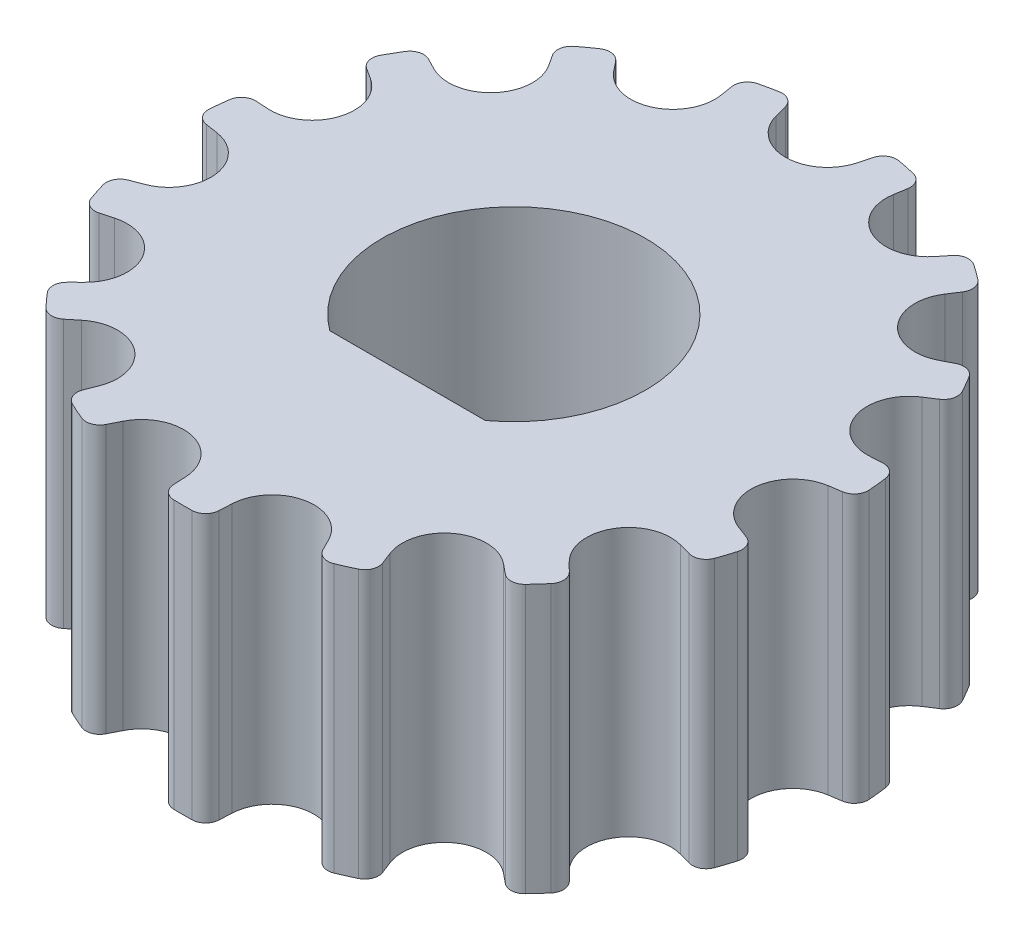
SolidWorks part; units mm, degrees
ref_plane "Front Plane" through (0, 0, 0) normal (0, 0, 1) x (1, 0, 0)
ref_plane "Top Plane" through (0, 0, 0) normal (0, 1, 0) x (1, 0, 0)
ref_plane "Right Plane" through (0, 0, 0) normal (1, 0, 0) x (0, 0, -1)
sketch "Sketch1" plane through (0, 0, 0) normal (0, 1, 0) x (1, 0, 0)
  circle A0 centre (0, 0) radius 7.162
  dimension "D1" = 14.3239
extrude "Boss-Extrude1" add sketch "Sketch1" along normal blind 5.8
sketch "Sketch2" plane through (0, 5.8, 0) normal (0, 1, 0) x (1, 0, 0)
  line L0 (0, 0) -> (0, 7.162) construction
  line L1 (-0.8799, 6.5598) -> (-0.95, 6.8255)
  line L2 (-2.913, 6.5428) -> (-2.913, 7.162)
  line L3 (-2.913, 7.162) -> (2.913, 7.162)
  line L4 (0.8799, 6.5598) -> (0.95, 6.8255)
  line L5 (2.913, 6.5428) -> (2.913, 7.162)
  circle A0 centre (0, 0) radius 7.162 construction
  arc A1 (0.8799, 6.5598) -> (-0.8799, 6.5598) centre (0, 6.792) cw
  arc A2 (-0.95, 6.8255) -> (-1.2943, 7.0441) centre (-1.2401, 6.749) ccw
  arc A4 (0.95, 6.8255) -> (1.2943, 7.0441) centre (1.2401, 6.749) cw
  arc A5 (-1.2943, 7.0441) -> (-2.913, 6.5428) centre (0, 0) ccw
  arc A6 (1.2943, 7.0441) -> (2.913, 6.5428) centre (0, 0) cw
  point P11 (0, 7.162)
  point P12 (0, 7.162)
  point P19 (0, 5.882)
  point P22 (0, 7.162)
  point P23 (1.5094, 6.5101)
  point P24 (2.8691, 6.4441)
  dimension "D3" = 0.3
  dimension "D5" = 0.91
  dimension "D2" = 0.95
  dimension "D4" = 1.28
  dimension "D6" = 24
extrude "Cut-Extrude1" cut sketch "Sketch2" against normal through all
pattern_circular "CirPattern1" count 15 over 360 about axis through (0, 5.8, 0) along (0, -1, 0) of "Cut-Extrude1"
sketch "Sketch3" plane through (0, 0, 0) normal (0, -1, 0) x (1, 0, 0)
  line L0 (1.683, 2.3) -> (-1.683, 2.3)
  arc A0 (-1.683, 2.3) -> (1.683, 2.3) centre (0, 0) ccw
  dimension "D1" = 5.7
  dimension "D2" = 2.3
extrude "Cut-Extrude2" cut sketch "Sketch3" against normal through all
equation "\"smallPulleyTeeth\"= 15"
equation "\"largePulleyTeeth\"= 30"
equation "\"eighthThick\"= 2.9mm"
equation "\"bushingDiam\"= 7.85mm"
equation "\"D1@Sketch1\"=3*\"smallPulleyTeeth\"/pi"
equation "\"D1@Boss-Extrude1\" = \"eighthThick\" * 2"
equation "\"D6@Sketch2\"=360/\"smallPulleyTeeth\""
equation "\"quarterThick\"=5.6mm"
equation "\"D1@CirPattern1\"=\"smallPulleyTeeth\""
